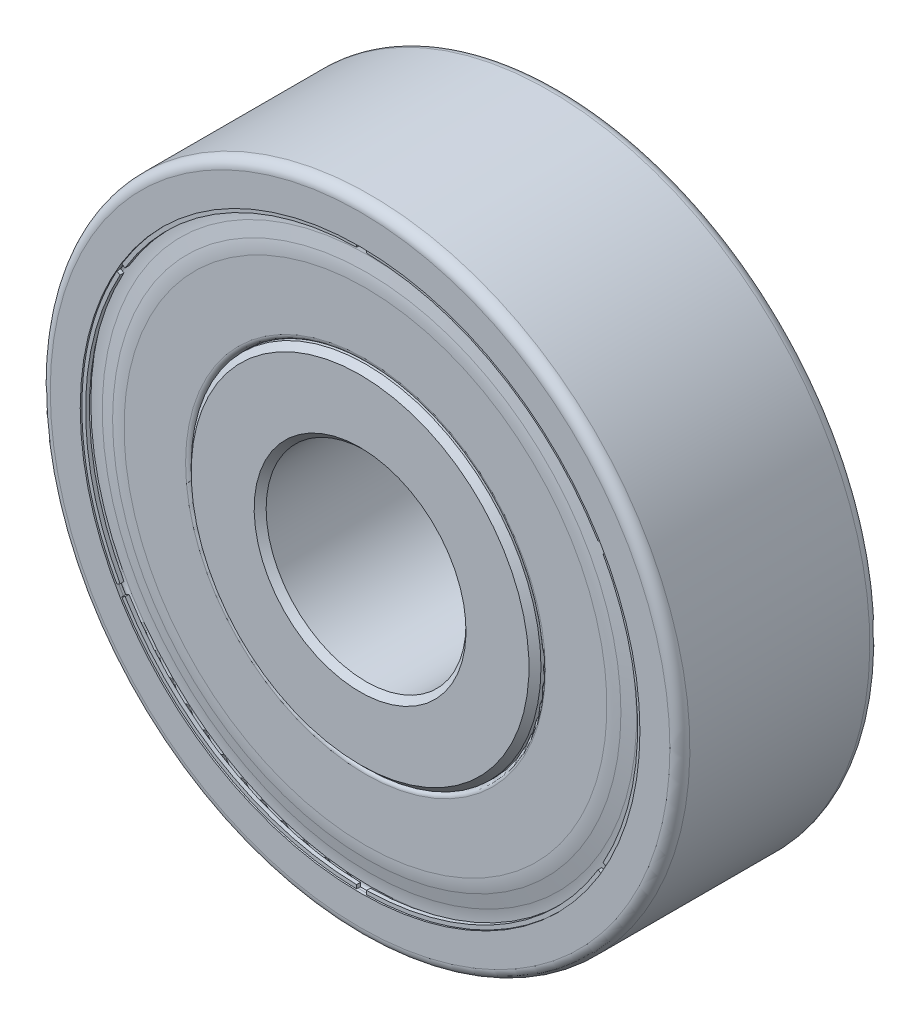
SolidWorks part; units mm, degrees
ref_plane "Front Plane" through (0, 0, 0) normal (0, 0, 1) x (1, 0, 0)
ref_plane "Top Plane" through (0, 0, 0) normal (0, 1, 0) x (1, 0, 0)
ref_plane "Right Plane" through (0, 0, 0) normal (1, 0, 0) x (0, 0, -1)
sketch "Sketch1" plane through (0, 0, 0) normal (0, 0, 1) x (1, 0, 0)
  line L0 (-8, 0) -> (-2.5, 0) construction
  line L1 (-2.5, 0) -> (2.5, 0) construction
  line L2 (2.5, 0) -> (8, 0) construction
  line L3 (0, 8) -> (0, 2.5) construction
  line L4 (0, 2.5) -> (0, 0) construction
  circle A0 centre (0, 0) radius 2.5 construction
  circle A1 centre (0, 0) radius 8 construction
  point P0 (0, 0)
  point P9 (0, 8)
  point P10 (0, 2.5)
  dimension "For Housing ID" = 16
  dimension "For Shaft Diameter" = 5
  dimension "OD" = 16
  dimension "ID" = 5
sketch "Sketch2" plane through (0, 0, 0) normal (1, 0, 0) x (0, 0, -1)
  line L1 (-2.5, -8) -> (2.5, -8) construction
  line L2 (-2.5, -8) -> (-2.5, 8) construction
  line L3 (-2.5, 8) -> (2.5, 8) construction
  line L4 (2.5, -8) -> (2.5, 8) construction
  line L5 (0, 8) -> (0, -8) construction
  line L6 (-2.5, 0) -> (2.5, 0) construction
  dimension "Width" = 5
sketch "Sketch3" plane through (0, 0, 0) normal (1, 0, 0) x (0, 0, -1)
  line L0 (-2.25, 8) -> (2.5, 8) construction
  line L1 (-2.5, 2.5) -> (2.5, 2.5)
  line L2 (-2.5, -8) -> (-2.5, 8) construction
  line L3 (2.5, -8) -> (2.5, 8) construction
  line L4 (-2.5, 2.5) -> (-2.5, 4.375)
  line L5 (-2.5, 4.375) -> (2.5, 4.375) construction
  line L6 (2.5, 4.375) -> (2.5, 2.5)
  line L7 (-2.5, 8) -> (-2.5, 7) construction
  line L8 (-2.5, 7) -> (2.5, 7) construction
  line L9 (2.5, 7) -> (2.5, 8) construction
  line L10 (0, 7) -> (0, 4.375) construction
  line L11 (0, 7.25) -> (0, 7) construction
  line L12 (0, 7.25) -> (0, 7.5) construction
  line L13 (0, 8) -> (0, 2.5) construction
  line L14 (0, 7.5) -> (0, 7.75) construction
  line L15 (0, 7.75) -> (0, 8) construction
  line L21 (2.5, 7) -> (2.425, 7)
  line L22 (-2.5, 7) -> (-2.425, 7)
  line L23 (-2.1769, 7.0217) -> (-2.1025, 6.6)
  line L24 (-2.1025, 6.6) -> (-1.2684, 6.6)
  line L25 (1.2684, 6.6) -> (2.1025, 6.6)
  line L26 (2.1025, 6.6) -> (2.1769, 7.0217)
  line L27 (-2.5, 4.375) -> (-0.8478, 4.375)
  line L28 (2.5, 4.375) -> (0.8478, 4.375)
  line L29 (-2.25, 8) -> (2.25, 8)
  line L31 (2.5, 7.75) -> (2.5, 7)
  line L33 (-2.5, 7.75) -> (-2.5, 7)
  circle A0 centre (0, 5.6875) radius 1.5625 construction
  arc A3 (-2.425, 7) -> (-2.1769, 7.0217) centre (-2.3, 7) cw
  arc A4 (2.1769, 7.0217) -> (2.425, 7) centre (2.3, 7) cw
  arc A5 (-1.2684, 6.6) -> (1.2684, 6.6) centre (0, 5.6875) cw
  arc A8 (-0.8478, 4.375) -> (0.8478, 4.375) centre (0, 5.6875) ccw
  arc A9 (-2.25, 8) -> (-2.5, 7.75) centre (-2.25, 7.75) ccw
  arc A10 (2.5, 7.75) -> (2.25, 8) centre (2.25, 7.75) ccw
  dimension "D1" = 3.125
  dimension "D5" = 0.125
  dimension "REF" = 5.5
  dimension "D2" = 1
  dimension "D3" = 0.075
  dimension "D4" = 10
  dimension "D6" = 0.4
revolve "Revolve1" add sketch "Sketch3" angle 360 about L6
sketch "Sketch7" plane through (0, 0, 0) normal (0, 0, 1) x (1, 0, 0)
  line L0 (0, 8) -> (0, 0) construction
  line L1 (0, 4.125) -> (0, 7.25) construction
  line L2 (-1.5024, 5.2582) -> (0, 0) construction
  line L3 (0, 0) -> (1.5024, 5.2582) construction
  circle A0 centre (0, 5.6875) radius 1.5625 construction
  point P8 (0, 4.125)
  dimension "Bearing Spacing" = 31.891
chamfer "Chamfer1" distance 0.15 angle 45 4 edges at (0, -2.5, -2.5) (0, -4.375, -2.5) (0, -2.5, 2.5) (0, -4.375, 2.5)
sketch "Sketch4" plane through (0, 0, 0) normal (1, 0, 0) x (0, 0, -1)
  line L0 (-2.425, 7) -> (-2.4625, 7)
  line L1 (-2.4625, 7) -> (-2.4625, 6.904)
  line L2 (-2.1025, 6.6) -> (-2.1769, 7.0217) construction
  line L3 (-2.4625, 7) -> (-2.5, 7) construction
  line L4 (-2.175, 7) -> (-2.175, 6.84)
  line L19 (-2.235, 6.84) -> (-2.175, 6.84) construction
  line L23 (-2.305, 6.2) -> (-2.305, 4.435) construction
  line L25 (-2.305, 4.435) -> (-1.5317, 4.435) construction
  line L26 (-1.5317, 4.435) -> (-1.5317, 4.375)
  line L28 (-1.5317, 4.375) -> (-2.365, 4.375) construction
  line L29 (-2.365, 4.375) -> (-2.365, 6.2) construction
  line L30 (-2.175, 6.84) -> (-2.305, 6.2)
  line L31 (-2.235, 6.84) -> (-2.235, 7)
  line L33 (-2.5, 4.375) -> (-0.8478, 4.375) construction
  line L35 (-2.4625, 6.904) -> (-2.365, 6.904)
  line L36 (-2.365, 6.904) -> (-2.365, 7)
  line L37 (-2.305, 5.3175) -> (-2.365, 5.3175) construction
  line L38 (-2.235, 6.84) -> (-2.365, 6.2)
  line L39 (-2.365, 6.904) -> (-2.365, 6.2) construction
  line L41 (-2.24, 4.375) -> (-1.5317, 4.375)
  line L42 (-2.24, 4.435) -> (-1.5317, 4.435)
  line L43 (-2.305, 4.5) -> (-2.305, 6.2)
  line L44 (-2.365, 6.2) -> (-2.365, 4.5)
  arc A0 (-2.175, 7) -> (-2.425, 7) centre (-2.3, 7) ccw
  arc A8 (-2.1769, 7.0217) -> (-2.425, 7) centre (-2.3, 7) ccw construction
  arc A9 (-2.235, 7) -> (-2.365, 7) centre (-2.3, 7) ccw
  arc A10 (-2.365, 4.5) -> (-2.24, 4.375) centre (-2.24, 4.5) ccw
  arc A11 (-2.305, 4.5) -> (-2.24, 4.435) centre (-2.24, 4.5) ccw
  point P24 (-2.1449, 6.84)
  dimension "D4" = 0.25
  dimension "D1" = 0.096
  dimension "D2" = 0.06
  dimension "D5" = 0.8333
  dimension "D6" = 0.16
  dimension "D3" = 0.64
revolve "Revolve2" add sketch "Sketch4" angle 360 about L6
fillet "Fillet1" radius 1.6 2 edges at (0, -6.2, 2.365) (0, -6.84, 2.235)
sketch "Sketch5" plane through (0, 0, 0) normal (1, 0, 0) x (0, 0, -1)
  line L0 (0, 7.25) -> (0, 4.125)
  circle A0 centre (0, 5.6875) radius 1.5625 construction
  arc A1 (0, 4.125) -> (0, 7.25) centre (0, 5.6875) ccw
revolve "Revolve3" add sketch "Sketch5" angle 360 about L0
pattern_circular "CirPattern1" count 6 over 360 about axis through (0, 0, 2.5) along (0, 0, -1) reverse direction yes of bodies 107
sketch "Sketch6" plane through (0, 0, 2.4625) normal (0, 0, 1) x (1, 0, 0)
  line L0 (0, 7) -> (0, 0) construction
  line L1 (-0.125, 6.9989) -> (-0.125, 6.9029)
  line L2 (0.125, 6.9989) -> (0.125, 6.9029)
  line L3 (-0.125, 6.9509) -> (0.125, 6.9509) construction
  arc A0 (0.125, 6.9029) -> (-0.125, 6.9029) centre (0, 0) ccw
  arc A1 (0.125, 6.9989) -> (-0.125, 6.9989) centre (0, 0) ccw
  circle A7 centre (0, 0) radius 7 construction
  circle A8 centre (0, 0) radius 6.904 construction
  circle A9 centre (0, 0) radius 7 construction
  circle A10 centre (0, 0) radius 6.904 construction
  point P13 (0, 6.9509)
  dimension "D1" = 0.25
extrude "Cut-Extrude1" cut sketch "Sketch6" against normal up to surface (0.0975 mm away) up to face at (0, -7, 2.365)
pattern_circular "CirPattern2" count 6 over 360 about axis through (0, 0, 2.5) along (0, 0, -1) of "Cut-Extrude1" reverse direction yes
mirror "Mirror2" about plane through (0, 0, 0) normal (0, 0, 1) of bodies 127 106
equation "\"D1@Sketch3\"=\"Width@Sketch2\"*.625"
equation "\"D2@Sketch3\"=\"OD@Sketch1\" * .0625"
equation "\"D3@Sketch3\"=\"Width@Sketch2\"*.015"
equation "\"D5@Sketch3\"=\"Width@Sketch2\"*.025"
equation "\"D6@Sketch3\" = \"OD@Sketch1\" * .025"
equation "\"D1@Chamfer1\"=\"Width@Sketch2\"*.03"
equation "\"D1@Fillet1\"=\"OD@Sketch1\"*.1"
equation "\"D1@CirPattern1\"=(360/\"Bearing Spacing@Sketch7\")-5"
equation "\"D1@CirPattern2\" = ( 360 / \"Bearing Spacing@Sketch7\" ) - 5"
equation "\"D1@Sketch4\"=\"OD@Sketch1\" *.006"
equation "\"D5@Sketch4\"=\"Width@Sketch2\"/6"
equation "\"D6@Sketch4\"=\"OD@Sketch1\" * .01"
equation "\"D3@Sketch4\"=\"OD@Sketch1\" *.04"
equation "\"D1@Sketch6\"=\"Width@Sketch2\"*.05"
equation "\"D4@Sketch4\"=\"Width@Sketch2\"*.05"
